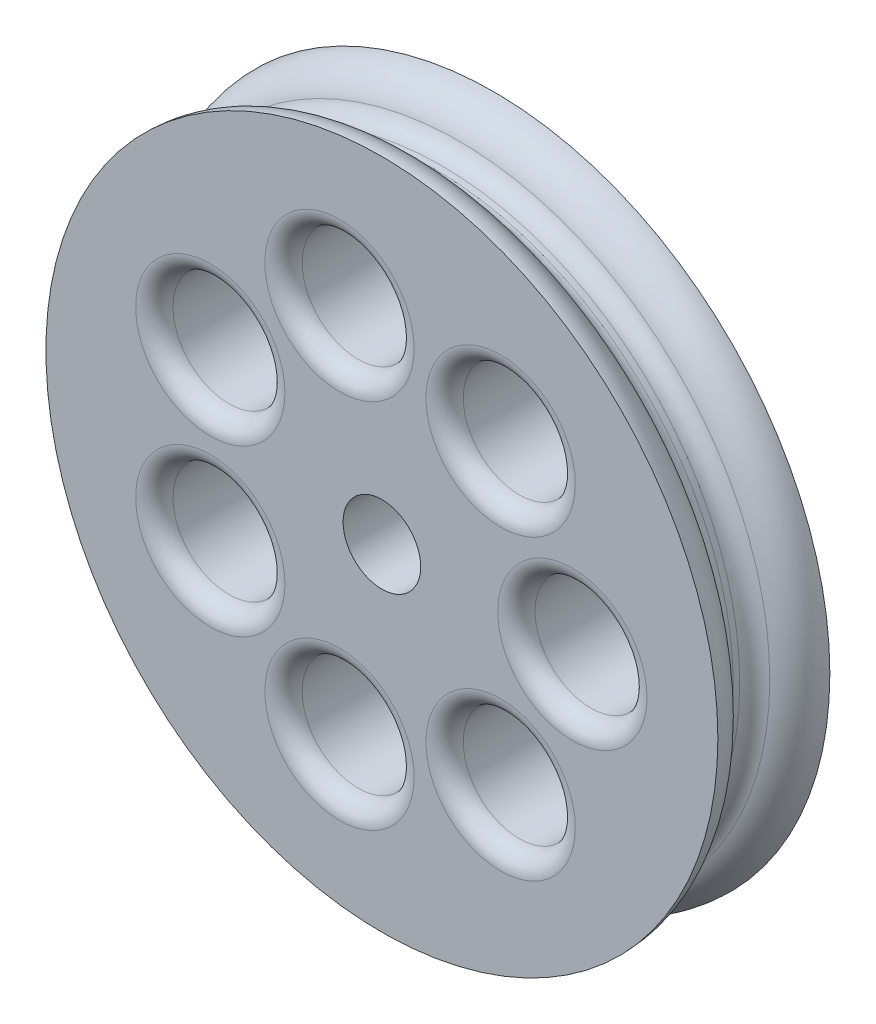
SolidWorks part; units mm, degrees
ref_plane "Спереди" through (0, 0, 0) normal (0, 0, 1) x (1, 0, 0)
ref_plane "Сверху" through (0, 0, 0) normal (0, 1, 0) x (1, 0, 0)
ref_plane "Справа" through (0, 0, 0) normal (1, 0, 0) x (0, 0, -1)
sketch "Эскиз1" plane through (0, 0, 0) normal (0, 0, 1) x (1, 0, 0)
  circle A0 centre (0, 0) radius 6
extrude "Бобышка-Вытянуть1" add sketch "Эскиз1" along normal blind 7
sketch "Эскиз2" plane through (0, 0, 7) normal (0, 0, 1) x (1, 0, 0)
  circle A0 centre (0, 0) radius 18
extrude "Бобышка-Вытянуть2" add sketch "Эскиз2" along normal blind 2
sketch "Эскиз3" plane through (0, 0, 9) normal (0, 0, 1) x (1, 0, 0)
  circle A0 centre (0, 0) radius 16
extrude "Бобышка-Вытянуть3" add sketch "Эскиз3" along normal blind 2
sketch "Эскиз4" plane through (0, 0, 11) normal (0, 0, 1) x (1, 0, 0)
  circle A0 centre (0, 0) radius 18
extrude "Бобышка-Вытянуть4" add sketch "Эскиз4" along normal blind 2
fillet "Скругление1" radius 2 2 edges at (18, 0, 11) (18, 0, 9)
fillet "Скругление2" radius 1 2 edges at (16, 0, 9) (16, 0, 11)
sketch "Эскиз5" plane through (0, 0, 0) normal (0, 0, -1) x (-1, 0, 0)
  circle A0 centre (0, 0) radius 2.08
extrude "Вырез-Вытянуть1" cut sketch "Эскиз5" against normal through all
chamfer "Фаска1" distance 1 angle 45 1 edges at (-2.08, 0, 0)
ref_plane "Плоскость1" through (6, 0, 0) normal (1, 0, 0) x (0, 0, -1)
sketch "Эскиз6" plane through (6, 0, 0) normal (1, 0, 0) x (0, 0, -1)
  line L0 (-13, 18) -> (-13, -18) construction
  circle A0 centre (-4, 0) radius 2.24
  dimension "D1" = 9
extrude "Вырез-Вытянуть2" cut sketch "Эскиз6" against normal blind 5
sketch "Эскиз8" plane through (0, 0, 7) normal (0, 0, -1) x (-1, 0, 0)
  circle A0 centre (-10.2036, 0) radius 3
extrude "Вырез-Вытянуть3" cut sketch "Эскиз8" against normal through all
fillet "Скругление3" radius 1 2 edges at (7.2036, 0, 7) (7.2036, 0, 13)
pattern_circular "Круговой массив2" count 7 over 360 about axis through (0, 0, 13) along (0, 0, -1) of "Скругление3", "Вырез-Вытянуть3"
fillet "Скругление4" radius 1 1 edges at (6, 0, 7)
